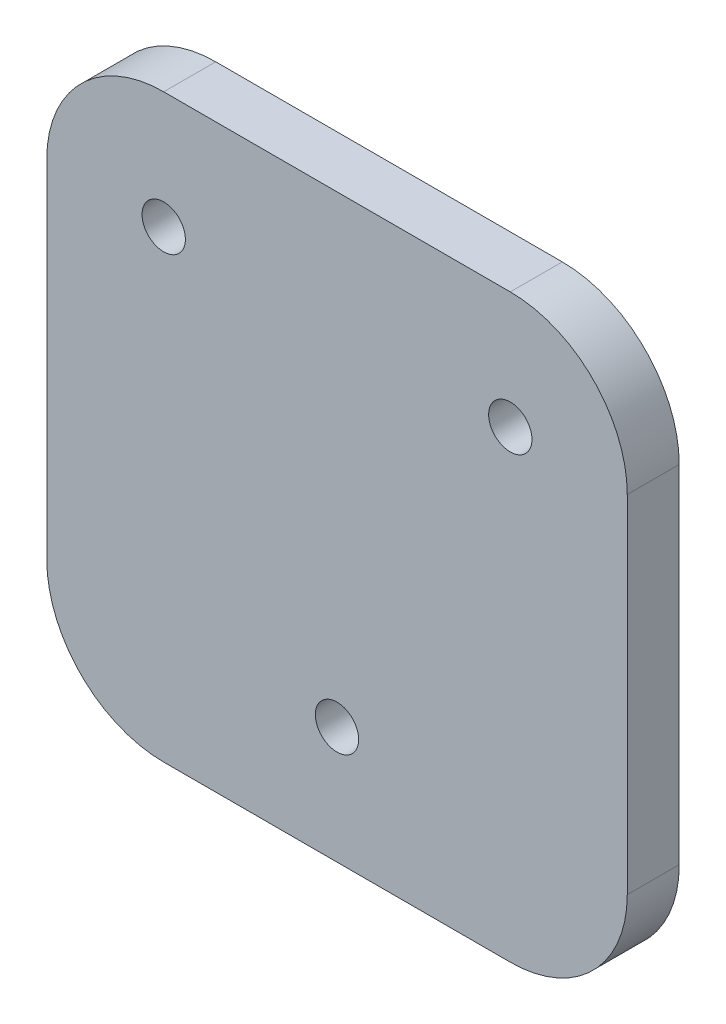
SolidWorks part; units mm, degrees
ref_plane "Plano frontal" through (0, 0, 0) normal (0, 0, 1) x (1, 0, 0)
ref_plane "Plano superior" through (0, 0, 0) normal (0, 1, 0) x (1, 0, 0)
ref_plane "Plano direito" through (0, 0, 0) normal (1, 0, 0) x (0, 0, -1)
sketch "Esboço1" plane through (0, 0, 0) normal (0, 0, 1) x (1, 0, 0)
  line L0 (-20, 33.5) -> (20, 33.5)
  line L1 (-20, 20) -> (20, 20) construction
  line L2 (-20, 20) -> (-20, -20) construction
  line L3 (-20, -20) -> (20, -20) construction
  line L4 (20, 20) -> (20, -20) construction
  line L5 (-20, 20) -> (20, -20) construction
  line L6 (-20, -20) -> (20, 20) construction
  line L9 (33.5, -20) -> (33.5, 20)
  line L10 (20, -33.5) -> (-20, -33.5)
  line L11 (-33.5, -20) -> (-33.5, 20)
  circle A0 centre (-20, 20) radius 2.5
  circle A1 centre (20, 20) radius 2.5
  circle A2 centre (0, -20) radius 2.5
  arc A3 (-20, 33.5) -> (-33.5, 20) centre (-20, 20) ccw
  arc A4 (33.5, 20) -> (20, 33.5) centre (20, 20) ccw
  arc A6 (20, -33.5) -> (33.5, -20) centre (20, -20) ccw
  arc A7 (-33.5, -20) -> (-20, -33.5) centre (-20, -20) ccw
  circle A8 centre (20, 20) radius 13.5 construction
  circle A9 centre (-20, 20) radius 13.5 construction
  point P0 (0, 0)
  point P13 (-8, 22)
  point P14 (0, -20)
  point P15 (32, 22)
  point P18 (12, -22)
  dimension "D3" = 5
  dimension "D1" = 40
  dimension "D2" = 40
  dimension "D4" = 11
extrude "Ressalto-extrusão1" add sketch "Esboço1" along normal blind 6
